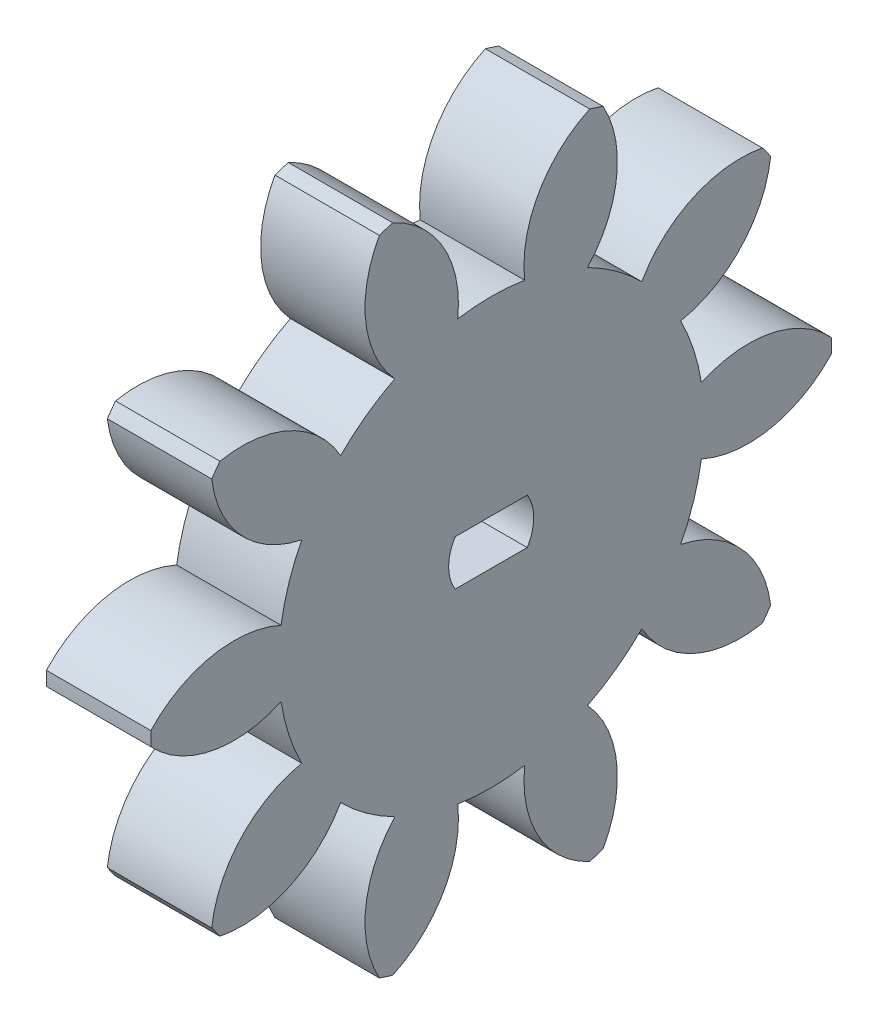
SolidWorks part; units mm, degrees
ref_plane "Plane1" through (0, 0, 0) normal (0, 0, 1) x (1, 0, 0)
ref_plane "Plane2" through (0, 0, 0) normal (0, 1, 0) x (1, 0, 0)
ref_plane "Plane3" through (0, 0, 0) normal (1, 0, 0) x (0, 0, -1)
sketch "HoldingSke" plane through (0, 0, 0) normal (0, 1, 0) x (1, 0, 0)
  line L0 (0, 0) -> (200.1129, -35.2853)
  line L1 (-15, 0) -> (100, 0) construction
  line L2 (0, 0) -> (-2.1039, 2.3779)
  line L3 (0, 0) -> (-11.863, 4.5341)
  line L4 (0, 0) -> (8.5048, 1.4996)
  line L5 (0, 0) -> (-47.5972, -17.7524)
  line L6 (0, 0) -> (-4.8428, -3.2675)
  line L7 (-2.1039, 2.3779) -> (8.8308, 51.9871)
  line L8 (-76.2, 54.61) -> (-71.1708, 54.61)
  line L9 (-71.009, 38.7566) -> (-53.1078, 45.2721)
  line L10 (-76.2, 71.12) -> (104.1128, 71.12)
  line L11 (0, 0) -> (-5.842, 0)
  line L12 (-76.2, 101.6) -> (-76.0857, 101.6)
  line L13 (24.9733, 27.94) -> (52.9518, 28.4284)
  line L14 (24.9733, 27.94) -> (24.9746, 27.94)
  line L15 (24.9733, 27.94) -> (100.4006, 29.5858)
  circle A0 centre (0, 0) radius 2.3812
  circle A1 centre (0, 0) radius 11.905
  circle A2 centre (0, 0) radius 38.1
  circle A3 centre (0, 0) radius 2.3812
  dimension "Num_teeth" = 10
  dimension "H" = 19.05
  dimension "Pitch_radius" = 180.3128
  dimension "Width" = 5.842
  dimension "Thickness" = 5.842
sketch "BasProSke" plane through (0, 0, 0) normal (0, 1, 0) x (1, 0, 0)
  line L0 (-10, 0) -> (60, 0) construction
  line L1 (0, 0) -> (0, 19.05)
  line L2 (0, 0) -> (5.842, 0)
  line L3 (5.842, 0) -> (5.842, 19.05)
  line L4 (5.842, 19.05) -> (0, 19.05)
  dimension "Thickness" = 5.842
  dimension "Diameter" = 38.1
revolve "Base-Revolve" add sketch "BasProSke" angle 360 about L0
sketch "TooCutSke" plane through (0, 0, 0) normal (1, 0, 0) x (0, 0, -1)
  line L1 (0, 0) -> (0, 107) construction
  line L2 (0, 0) -> (-2.683, 15.6466) construction
  line L3 (0, 0) -> (-9.7093, 29.8821) construction
  line L4 (-2.683, 15.6466) -> (-4.8546, 14.941) construction
  arc A0 (1.8735, 11.7566) -> (-1.8735, 11.7566) centre (0, 0) ccw
  arc A1 (5.5485, 18.2506) -> (-5.5485, 18.2506) centre (0, 0) ccw
  circle A2 centre (0, 0) radius 15.875 construction
  circle A3 centre (0, 0) radius 14.9176 construction
  arc A4 (-1.8735, 11.7566) -> (-5.5485, 18.2506) centre (-8.183, 12.4729) ccw
  arc A5 (5.5485, 18.2506) -> (1.8735, 11.7566) centre (8.183, 12.4729) ccw
extrude "ToothCut" cut sketch "TooCutSke" along normal through all
fillet "Breaks" [suppressed] radius 0.0635 tangent propagation no
fillet "RootFillets" [suppressed] radius 0.795
pattern_circular "TeethCuts" count 10 every 36 about axis through (-10, 0, 0) along (1, 0, 0) of "ToothCut", "RootFillets", "Breaks"
sketch "HubNeaOneSke" plane through (0, 0, 0) normal (-1, 0, 0) x (0, 0, 1)
  circle A0 centre (0, 0) radius 11.905
  dimension "Diameter" = 23.81
extrude "HubNearOne" [suppressed] add sketch "HubNeaOneSke" along normal blind 44.9581
sketch "HubNeaBotSke" plane through (0, 0, 0) normal (-1, 0, 0) x (0, 0, 1)
  circle A0 centre (0, 0) radius 11.905
  dimension "Diameter" = 23.81
extrude "HubNearBoth" [suppressed] add sketch "HubNeaBotSke" along normal blind 22.479
ref_plane "FarPln" through (5.842, 0, 0) normal (1, 0, 0) x (0, 0, -1)
sketch "HubFarSke" plane through (5.842, 0, 0) normal (1, 0, 0) x (0, 0, -1)
  circle A0 centre (0, 0) radius 11.905
  dimension "Diameter" = 23.81
extrude "HubFar" [suppressed] add sketch "HubFarSke" along normal blind 22.479
sketch "BorSke" plane through (0, 0, 0) normal (1, 0, 0) x (0, 0, -1)
  circle A0 centre (0, 0) radius 2.3812
  dimension "Diameter" = 4.7625
extrude "Bore" cut sketch "BorSke" along normal mid plane 101.6001
sketch "KeySke" plane through (0, 0, 0) normal (1, 0, 0) x (0, 0, -1)
  line L0 (-0.127, 0) -> (-0.127, 2.6479)
  line L1 (-0.127, 2.6479) -> (0.127, 2.6479)
  line L2 (0.127, 2.6479) -> (0.127, 0)
  line L3 (0, 0) -> (0, 34) construction
  line L4 (-0.127, 0) -> (0.127, 0)
  dimension "Width" = 0.254
extrude "Keyway" [suppressed] cut sketch "KeySke" along normal mid plane 101.6001
pattern_circular "Keyway2" [suppressed] count 2 every 90 about axis through (-10, 0, 0) along (1, 0, 0) reverse direction yes
sketch "Sketch1" plane through (5.842, 0, 0) normal (1, 0, 0) x (0, 0, -1)
  line L0 (-4.4067, 4.572) -> (4.4067, 4.572)
  arc A0 (4.4067, 4.572) -> (-4.4067, 4.572) centre (0, 0) ccw
  point P5 (0, -6.35)
  dimension "D1" = 10.922
extrude "Boss-Extrude1" add sketch "Sketch1" against normal up to surface (5.842 mm away) up to face at (0, 0, -2.3812)
sketch "Sketch2" plane through (5.842, 0, 0) normal (1, 0, 0) x (0, 0, -1)
  line L0 (-2.177, 1.27) -> (2.177, 1.27)
  line L1 (-2.177, -1.27) -> (2.177, -1.27)
  line L2 (0, 1.27) -> (0, -1.27) construction
  arc A0 (-2.177, -1.27) -> (2.177, -1.27) centre (0, 0) ccw
  arc A1 (2.177, 1.27) -> (-2.177, 1.27) centre (0, 0) ccw
  point P9 (0, 0)
  point P10 (0, 0)
  dimension "D1" = 2.54
extrude "Boss-Extrude3" add sketch "Sketch2" against normal up to surface (5.842 mm away) up to face at (0, 0, -2.3812)
equation "' \"Pitch@HoldingSke\" = 4"
equation "' \"Num_teeth@HoldingSke\" = 12"
equation "' \"Ap@HoldingSke\" =  20"
equation "' \"Ap@HoldingSke\" = 20"
equation "' \"Width@HoldingSke\" = 0.5"
equation "' \"Hub_dia@HoldingSke\"= 1"
equation "' \"Hub_dia@HoldingSke\" = 1"
equation "' \"Overall_len@HoldingSke\" = 1.0"
equation "' \"Bore@HoldingSke\" = 0.75"
equation "' \"T_dim@HoldingSke\" = 0.85"
equation "' \"Width@KeySke\" = 0.25"
equation "' \"Show_teeth@HoldingSke\" = 13"
equation "' \"Backlash@HoldingSke\" = 0.009"
equation "' \"Addendum_fac@HoldingSke\" = 1.0"
equation "' \"Dedendum_fac@HoldingSke\" = 1.25"
equation "' \"Dedendum_add@HoldingSke\" = 0.00005"
equation "' \"Clearance_fac@HoldingSke\" = 0.25"
equation "' \"Pitch@HoldingSke\" = 0.5"
equation "' \"Num_teeth@HoldingSke\" = 23"
equation "' \"Show_teeth@HoldingSke\" = 23"
equation "' \"Backlash@HoldingSke\" = 0.0375"
equation "\"Overcut_dia@TooCutSke\" = (\"Num_teeth@HoldingSke\" + 2 * \"Addendum_fac@HoldingSke\") / \"Pitch@HoldingSke\" + 0.002"
equation "\"Pitch_dia@TooCutSke\" = \"Num_teeth@HoldingSke\" / \"Pitch@HoldingSke\""
equation "\"Base_dia@TooCutSke\" = \"Num_teeth@HoldingSke\" / \"Pitch@HoldingSke\" * cos((\"Ap@HoldingSke\"  * 3.14159265 / 180))"
equation "\"Root_dia@TooCutSke\" = (\"Num_teeth@HoldingSke\" + 2) / \"Pitch@HoldingSke\" - 2 * (\"Addendum_fac@HoldingSke\" + \"Dedendum_fac@HoldingSke\") / \"Pitch@HoldingSke\" - \"Dedendum_add@HoldingSke\" * 2"
equation "\"Half_ang@TooCutSke\" = 180 / \"Num_teeth@HoldingSke\""
equation "\"Half_CT@TooCutSke\" = \"Num_teeth@HoldingSke\" / \"Pitch@HoldingSke\" * sin((3.14159265 / 2 / \"Num_teeth@HoldingSke\")) / 2 - 7 * \"Backlash@HoldingSke\" / 4"
equation "\"Flank_rad@TooCutSke\" = \"Num_teeth@HoldingSke\" / \"Pitch@HoldingSke\" / 5"
equation "\"Radius@RootFillets\" = \"Clearance_fac@HoldingSke\" / \"Pitch@HoldingSke\" + \"Dedendum_add@HoldingSke\""
equation "\"Break_rad@Breaks\" = 0.02 / \"Pitch@HoldingSke\""
equation "\"Thickness@HoldingSke\" = \"Width@HoldingSke\""
equation "\"OAL@HoldingSke\" = \"Thickness@HoldingSke\""
equation "\"MHD@HoldingSke\" = (\"Num_teeth@HoldingSke\" + 2) / \"Pitch@HoldingSke\" - 2 * (\"Addendum_fac@HoldingSke\" + \"Dedendum_fac@HoldingSke\")  / \"Pitch@HoldingSke\" - \"Dedendum_add@HoldingSke\" * 2"
equation "\"MBD@HoldingSke\" = (\"Num_teeth@HoldingSke\" + 2) / \"Pitch@HoldingSke\" - 2 * (\"Addendum_fac@HoldingSke\" + \"Dedendum_fac@HoldingSke\")  / \"Pitch@HoldingSke\" - \"Dedendum_add@HoldingSke\" * 2 - 0.002"
equation "\"MHD@HoldingSke\" = ((sgn( \"MHD@HoldingSke\" - \"Hub_dia@HoldingSke\" )-1)*( \"MHD@HoldingSke\" - \"Hub_dia@HoldingSke\" ))/-2+ \"Hub_dia@HoldingSke\""
equation "\"MBD@HoldingSke\" = ((sgn( \"MBD@HoldingSke\" - \"Bore@HoldingSke\" )-1)*( \"MBD@HoldingSke\" - \"Bore@HoldingSke\" ))/-2+ \"Bore@HoldingSke\""
equation "\"OAL@HoldingSke\" = ((sgn( \"OAL@HoldingSke\" - \"Overall_len@HoldingSke\" )+1)*( \"OAL@HoldingSke\" - \"Overall_len@HoldingSke\" ))/2 + \"Overall_len@HoldingSke\" + 0.000002"
equation "\"Num_teeth@TeethCuts\" = int( \"Show_teeth@HoldingSke\" ) + 1"
equation "\"Num_teeth@TeethCuts\" = ((sgn( \"Num_teeth@TeethCuts\" - \"Num_teeth@HoldingSke\" )-1)*( \"Num_teeth@TeethCuts\" - \"Num_teeth@HoldingSke\" ))/-2+ \"Num_teeth@HoldingSke\""
equation "\"Num_teeth@TeethCuts\" = ((sgn( \"Num_teeth@TeethCuts\" - 2.0)+1)*( \"Num_teeth@TeethCuts\" - 2.0))/2 +2.0"
equation "\"Angle@TeethCuts\" = 360.0 / \"Num_teeth@HoldingSke\""
equation "\"Diameter@BasProSke\" = (\"Num_teeth@HoldingSke\" + 2 * \"Addendum_fac@HoldingSke\") / \"Pitch@HoldingSke\""
equation "\"Thickness@BasProSke\"  = \"Thickness@HoldingSke\""
equation "' \"Fillet_rad@BasProSke\" =  \"Thickness@HoldingSke\" * 0.05"
equation "' \"Fillet_rad@BasProSke\" = \"Thickness@HoldingSke\" * 0.05"
equation "\"MHD@HoldingSke\" = ((sgn( \"MHD@HoldingSke\" - \"Root_dia@TooCutSke\" )-1)*( \"MHD@HoldingSke\" - \"Root_dia@TooCutSke\" ))/-2+ \"Root_dia@TooCutSke\""
equation "\"Diameter@HubNeaOneSke\" = \"MHD@HoldingSke\""
equation "\"Length@HubNearOne\" = \"OAL@HoldingSke\" - \"Thickness@BasProSke\""
equation "\"Diameter@HubNeaBotSke\" = \"MHD@HoldingSke\""
equation "\"Length@HubNearBoth\" = ( \"OAL@HoldingSke\" - \"Thickness@BasProSke\" ) / 2.0"
equation "\"Thickness@FarPln\" = \"Thickness@BasProSke\""
equation "\"Diameter@HubFarSke\" = \"MHD@HoldingSke\""
equation "\"Length@HubFar\" = ( \"OAL@HoldingSke\" - \"Thickness@BasProSke\" ) / 2.0"
equation "\"Diameter@BorSke\" = \"MBD@HoldingSke\""
equation "\"D1@Bore\" = \"OAL@HoldingSke\" * 2.0"
equation "\"D1@Keyway\" = \"OAL@HoldingSke\" * 2.0"
equation "\"Offset@KeySke\" = \"T_dim@HoldingSke\" - \"MBD@HoldingSke\" / 2.0"
